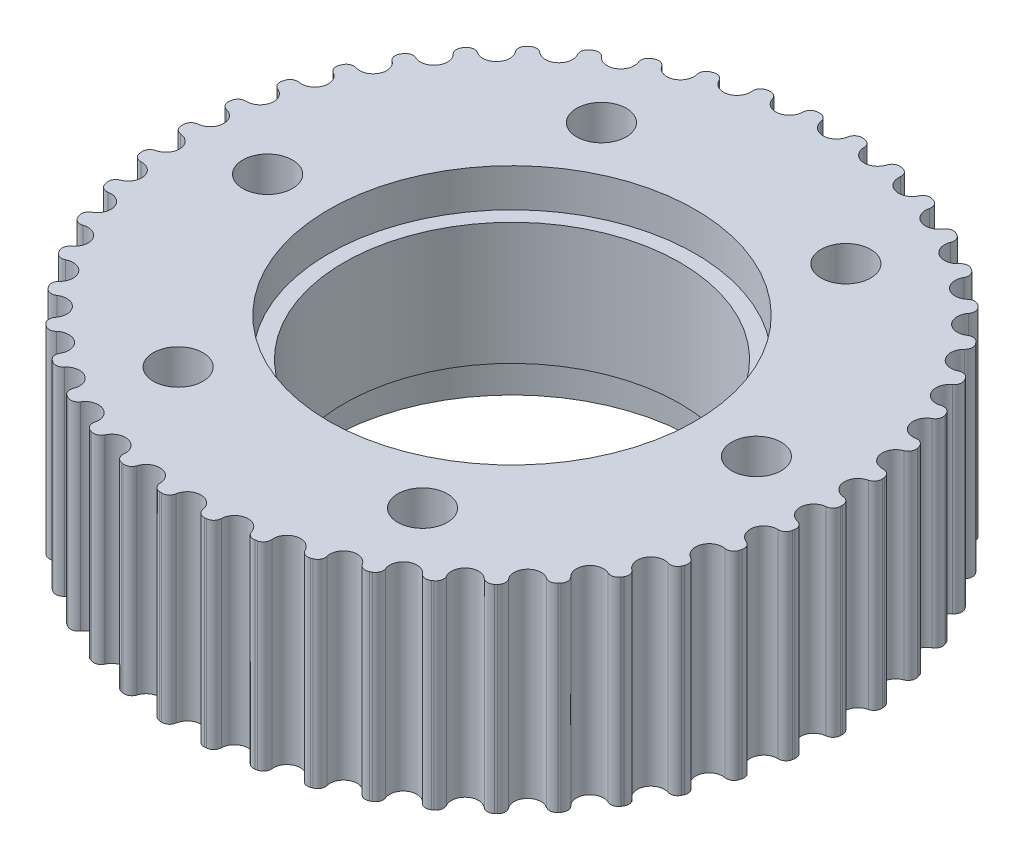
SolidWorks part; units mm, degrees
ref_plane "Front Plane" through (0, 0, 0) normal (0, 0, 1) x (1, 0, 0)
ref_plane "Top Plane" through (0, 0, 0) normal (0, 1, 0) x (1, 0, 0)
ref_plane "Right Plane" through (0, 0, 0) normal (1, 0, 0) x (0, 0, -1)
sketch "Sketch1" plane through (0, 0, 0) normal (0, 1, 0) x (1, 0, 0)
  line L0 (0, 0) -> (0, 21.582) construction
  line L1 (0, 0) -> (2.8938, 21.0541) construction
  circle A0 centre (0, 0) radius 21.582 construction
  circle A1 centre (0, 0) radius 20.362 construction
  circle A2 centre (0, 21.252) radius 0.89 construction
  circle A5 centre (2.8938, 21.0541) radius 0.89 construction
  arc A6 (0, 20.362) -> (0.8793, 21.1145) centre (0, 21.252) ccw
  arc A7 (0.8793, 21.1145) -> (1.4059, 21.5362) centre (1.3733, 21.0373) cw
  arc A8 (1.5397, 21.527) -> (2.004, 21.0376) centre (1.5041, 21.0283) cw
  arc A9 (2.7726, 20.1724) -> (2.004, 21.0376) centre (2.8938, 21.0541) cw
  arc A10 (1.4059, 21.5362) -> (1.5397, 21.527) centre (0, 0) cw
  arc A11 (0, 20.362) -> (2.7726, 20.1724) centre (0, 0) ccw
  dimension "D1" = 43.1641
  dimension "D3" = 1.78
  dimension "D4" = 0.5
  dimension "D2" = 1.22
  dimension "D5" = 7.826
extrude "Boss-Extrude1" add sketch "Sketch1" along normal mid plane 13 contours A6 A11 A9 A8 A7 region at (0.0017, 0, -0.025)
ref_axis "Axis1" through (0, 3.3, 0) along (0, -1, 0)
pattern_circular "CirPattern1" count 46 over 360 about axis through (0, 3.3, 0) along (0, -1, 0) of "Boss-Extrude1"
sketch "Sketch2" plane through (0, 0, 0) normal (1, 0, 0) x (0, 0, -1)
  line L10 (0, 6.5) -> (22.7568, 6.5) construction
  line L11 (0, 6.5) -> (0, 8.0875) construction
  line L12 (0, 8.0875) -> (22.7568, 8.0875) construction
  line L15 (22.7568, 6.5) -> (22.7568, 8.0875) construction
  line L20 (0, 3.3) -> (0, -3.3) construction
  line L22 (22.7568, 8.0875) -> (0, 8.0875)
  line L23 (22.7568, 8.0875) -> (22.7568, 6.5)
  line L24 (22.7568, 6.5) -> (0, 6.5)
  line L25 (0, 8.0875) -> (0, 6.5)
  dimension "D1" = 1.5875
  dimension "D2" = 22.7568
  dimension "D3" = 6.5
revolve "Revolve3" [suppressed] add sketch "Sketch2" angle 360 about axis through (0, 3.3, 0) along (0, -1, 0)
mirror "Mirror1" [suppressed] about plane through (0, 0, 0) normal (0, 1, 0)
sketch "Sketch3" plane through (0, 0, 0) normal (0, -1, 0) x (-1, 0, 0)
  circle A0 centre (0, 0) radius 11
  dimension "D1" = 22
extrude "Cut-Extrude1" cut sketch "Sketch3" against normal through all both and the other way through all
sketch "Sketch4" plane through (0, 0, 0) normal (0, 1, 0) x (1, 0, 0)
  circle A0 centre (-16, 0) radius 1.625
  point P3 (-16, 0)
  dimension "D1" = 3.25
extrude "Cut-Extrude2" cut sketch "Sketch4" against normal through all both and the other way through all
pattern_circular "CirPattern2" count 6 over 360 about axis through (0, 6.5, 0) along (0, -1, 0) of "Cut-Extrude2"
sketch "Sketch7" plane through (0, 0, 0) normal (0, 1, 0) x (1, 0, 0)
  circle A0 centre (0, 0) radius 12
  dimension "D1" = 24
extrude "Cut-Extrude3" cut sketch "Sketch7" along normal through all from offset 4
mirror "Mirror2" about plane through (0, 0, 0) normal (0, 1, 0) of "Cut-Extrude3"
equation "\"TEETH_NUM\"= 46"
equation "\"TOOTH_PITCH\"= 3mm"
equation "\"PITCH_LINE_OFFSET\"= .015in"
equation "\"DIAMETER_PER_GROOVE\"= \"OUTSIDE_DIAMETER\" / \"TEETH_NUM\" * 1in"
equation "\"PITCH_DIAMETER\"= ( ( \"TEETH_NUM\" * 3 - 1.31 ) / 3.1415 + .415 ) * 1mm"
equation "\"OUTSIDE_DIAMETER\"= \"PITCH_DIAMETER\" - \"PITCH_LINE_OFFSET\" * 2"
equation "\"D1@Sketch1\"=\"OUTSIDE_DIAMETER\""
equation "\"TOOTH_HEIGHT\"= 1.22mm"
equation "\"D2@Sketch1\"=\"TOOTH_HEIGHT\""
equation "\"TOOTH_DIAMETER\"= 1.78mm"
equation "\"INTERNAL_RADIUS\"= .5mm"
equation "\"D3@Sketch1\"=\"TOOTH_DIAMETER\""
equation "\"D5@Sketch1\"=360 / \"TEETH_NUM\""
equation "\"D4@Sketch1\"=\"INTERNAL_RADIUS\""
equation "\"D1@CirPattern1\"=\"TEETH_NUM\""
equation "\"BELT_GAP\"= 13mm"
equation "\"D2@Sketch2\"=\"PITCH_DIAMETER\"/2+1/32"
equation "\"D3@Sketch2\"=\"BELT_GAP\"/2"
equation "\"ID\"= \"bearing_OD\" - 2mm"
equation "\"D1@Sketch3\"=\"ID\""
equation "\"D1@Boss-Extrude1\"=\"BELT_GAP\""
equation "\"bearing_thickness\"= 5mm"
equation "\"Outside_Plate_Thickness\"= 2.5mm"
equation "\"Recess_Height\"= \"BELT_GAP\" / 2 + \"Outside_Plate_Thickness\" - \"bearing_thickness\""
equation "\"bearing_OD\"= 24mm"
equation "\"D1@Sketch7\"=\"bearing_OD\""
equation "\"D19@Cut-Extrude3\"=\"Recess_Height\""
